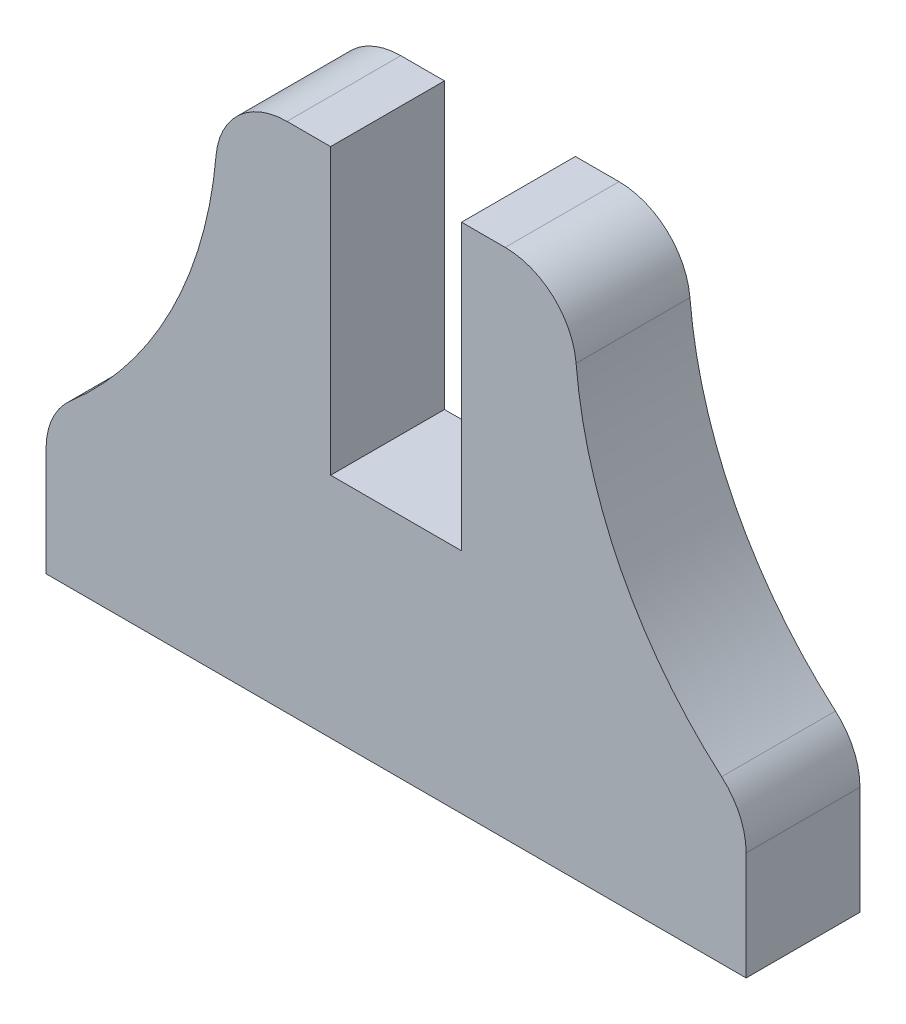
SolidWorks part; units mm, degrees
ref_plane "Front Plane" through (0, 0, 0) normal (0, 0, 1) x (1, 0, 0)
ref_plane "Top Plane" through (0, 0, 0) normal (0, 1, 0) x (1, 0, 0)
ref_plane "Right Plane" through (0, 0, 0) normal (1, 0, 0) x (0, 0, -1)
sketch "Sketch1" plane through (0, 0, 0) normal (0, 0, 1) x (1, 0, 0)
  line L0 (-4, -181.6843) -> (0, -181.6843) construction
  line L2 (-4.3, -163.6843) -> (-4.3, -173.6843)
  line L3 (-4.3, -181.6843) -> (0.3, -181.6843)
  line L4 (0.3, -163.6843) -> (0.3, -173.6843)
  line L5 (-2, -163.6843) -> (-2, -121.6843) construction
  line L6 (-4, -121.6843) -> (0, -121.6843) construction
  line L7 (0, -171.6843) -> (0, -124.1843) construction
  line L8 (0.3, -181.6843) -> (10.3, -181.6843)
  line L9 (0.3, -163.6843) -> (1.8347, -163.6843)
  line L10 (10.3, -181.6843) -> (10.3, -177.8791)
  line L11 (-14.3, -181.6843) -> (-14.3, -177.8791)
  line L12 (-4.3, -163.6843) -> (-5.8347, -163.6843)
  line L13 (-4.3, -181.6843) -> (-14.3, -181.6843)
  line L14 (-4.3, -173.6843) -> (0.3, -173.6843)
  arc A0 (4.3252, -165.9666) -> (9.4383, -175.9907) centre (19.2682, -164.6605) ccw
  arc A1 (10.3, -177.8791) -> (9.4383, -175.9907) centre (7.8, -177.8791) ccw
  arc A2 (1.8347, -163.6843) -> (4.3252, -165.9666) centre (1.8347, -166.1843) cw
  arc A3 (-5.8347, -163.6843) -> (-8.3252, -165.9666) centre (-5.8347, -166.1843) ccw
  arc A4 (-14.3, -177.8791) -> (-13.4383, -175.9907) centre (-11.8, -177.8791) cw
  arc A5 (-8.3252, -165.9666) -> (-13.4383, -175.9907) centre (-23.2682, -164.6605) cw
  point P18 (10.3, -176.6843)
  point P21 (4.3, -163.6843)
  point P30 (-8.3, -163.6843)
  point P31 (-14.3, -176.6843)
  point P34 (0.3, -175.9907)
  point P35 (-4.3, -175.9907)
  point P36 (0, -166.1843)
  point P37 (-2, -173.6843)
  dimension "D6" = 15
  dimension "D7" = 2.5
  dimension "D1" = 18
  dimension "D2" = 0.3
  dimension "D3" = 10
  dimension "D4" = 4
  dimension "D5" = 5
  dimension "D8" = 8
extrude "Boss-Extrude1" add sketch "Sketch1" along normal blind 4
